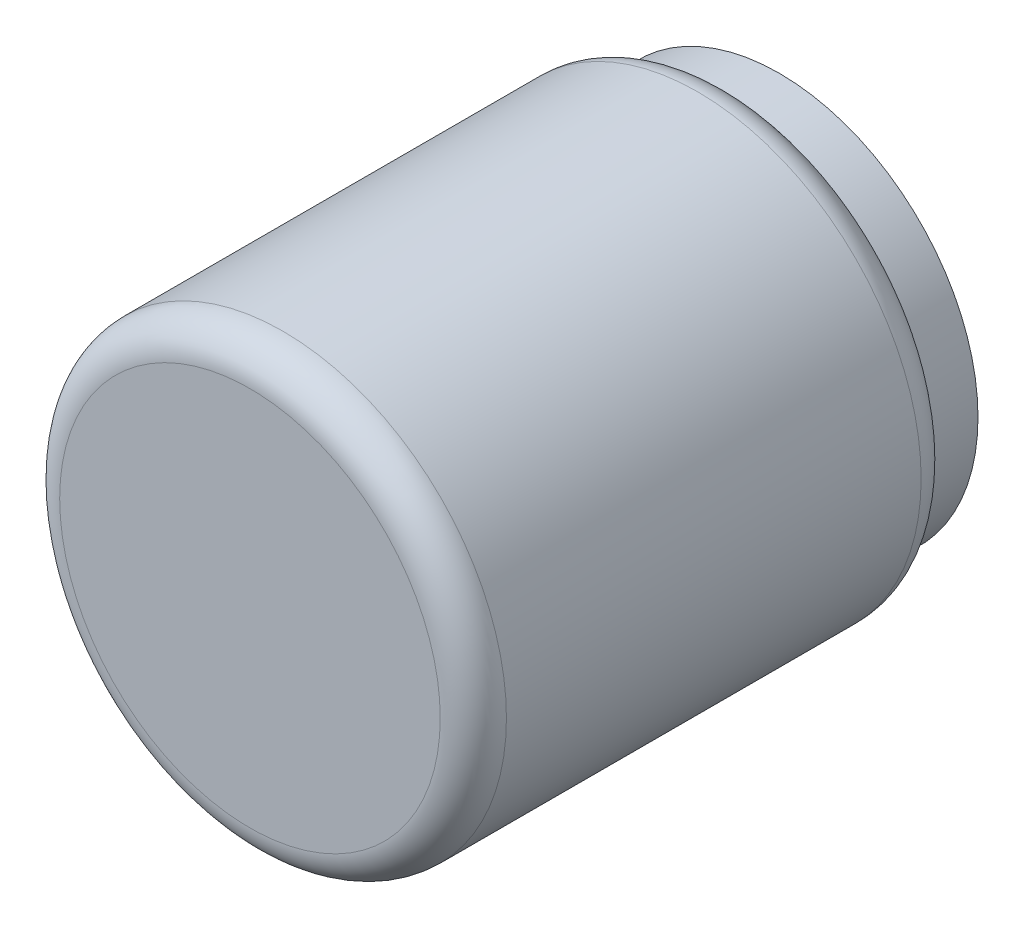
SolidWorks part; units mm, degrees
ref_plane "Front Plane" through (0, 0, 0) normal (0, 0, 1) x (1, 0, 0)
ref_plane "Top Plane" through (0, 0, 0) normal (0, 1, 0) x (1, 0, 0)
ref_plane "Right Plane" through (0, 0, 0) normal (1, 0, 0) x (0, 0, -1)
sketch "Sketch1" plane through (0, 0, 0) normal (0, 0, 1) x (1, 0, 0)
  circle A0 centre (0, 0) radius 13.5
  dimension "D1" = 27
extrude "Boss-Extrude1" add sketch "Sketch1" along normal blind 32
fillet "Fillet1" radius 2 1 edges at (13.5, 0, 32)
sketch "Sketch2" plane through (0, 0, 0) normal (0, 0, -1) x (-1, 0, 0)
  circle A0 centre (0, 0) radius 12
  circle A1 centre (0, 0) radius 14.6344
  dimension "D1" = 24
extrude "Cut-Extrude1" cut sketch "Sketch2" against normal blind 3
fillet "Fillet2" radius 2 1 edges at (-13.5, 0, 3)
sketch "Sketch3" plane through (0, 0, 0) normal (0, 0, -1) x (-1, 0, 0)
  line L0 (0, 15.2087) -> (0, -15.7713) construction
  line L1 (-18.4835, 0) -> (16.4343, 0) construction
